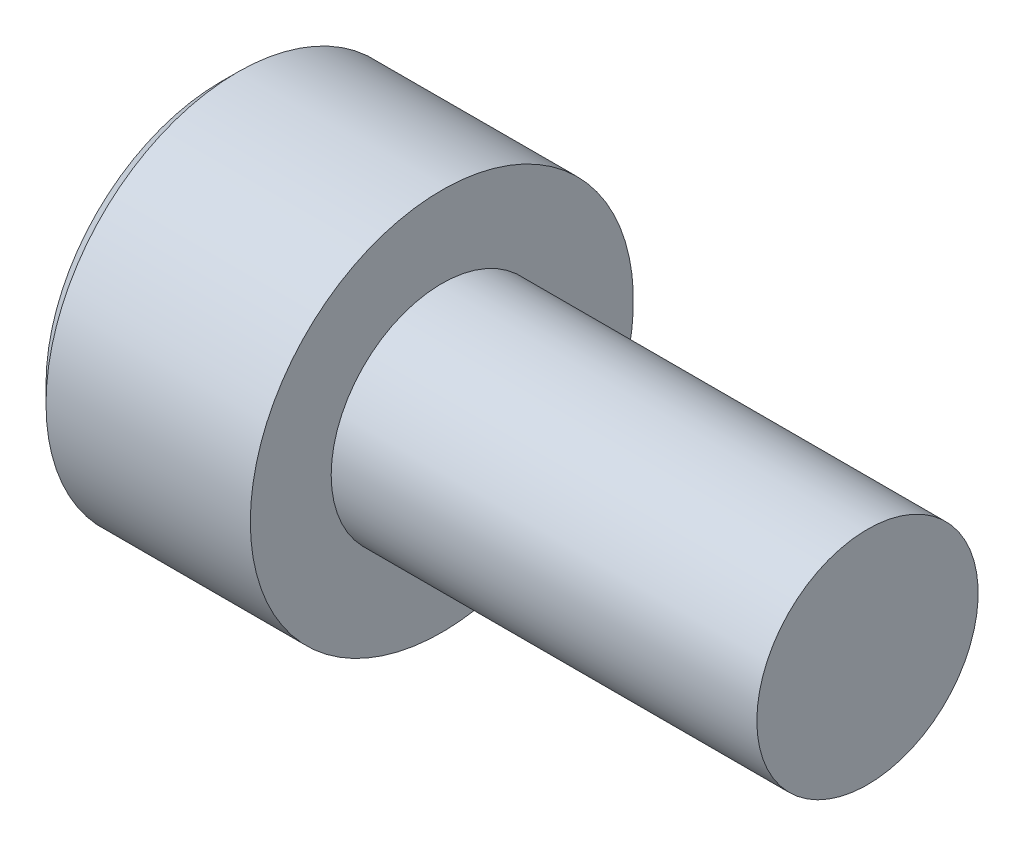
SolidWorks part; units mm, degrees
material "SCM435"
ref_plane "Front Plane" through (0, 0, 0) normal (0, 0, 1) x (1, 0, 0)
ref_plane "Top Plane" through (0, 0, 0) normal (0, 1, 0) x (1, 0, 0)
ref_plane "Right Plane" through (0, 0, 0) normal (1, 0, 0) x (0, 0, -1)
sketch "Sketch1" plane through (0, 0, 0) normal (0, 0, 1) x (1, 0, 0)
  line L2 (-2.6, 0) -> (5, 0)
  line L3 (5, 0) -> (5, 1.3)
  line L4 (5, 1.3) -> (0, 1.3)
  line L5 (0, 1.3) -> (0, 2.25)
  line L6 (0, 2.25) -> (-2.6, 2.25)
  line L7 (-2.6, 2.25) -> (-2.6, 0)
  line L8 (-2.6, 0) -> (5, 0) construction
  line L9 (0, 0) -> (0, 2.25) construction
  dimension "E" = 2.6
  dimension "L" = 5
  dimension "A" = 4.5
  dimension "M" = 2.6
revolve "Revolve1" add sketch "Sketch1" angle 360 about L8
cosmetic thread "Thread1" parameters "L_s"=5, "ATD"=2.1129
chamfer "Chamfer1" distance 0.2 angle 45 1 edges at (-2.6, 0, 2.25)
sketch "Sketch2" plane through (0, 0, 0) normal (0, 0, 1) x (1, 0, 0)
  line L0 (-0.8991, 0) -> (-1.5, 1)
  line L1 (-2.6, 0) -> (5, 0) construction
  line L2 (-1.5, 1) -> (-2.6, 1)
  line L3 (-2.6, 2.25) -> (-2.6, 0) construction
  line L4 (-2.6, 1) -> (-2.6, 0)
  line L5 (-2.6, 0) -> (-0.8991, 0) construction
  line L6 (-0.8991, 0) -> (-2.6, 0)
  dimension "FIX_3" = 59
  dimension "MSM_1" = 1.1
  dimension "B" = 2
revolve "Cut-Revolve1" cut sketch "Sketch2" angle 360 about L5
sketch "Sketch3" plane through (-2.6, 0, 0) normal (-1, 0, 0) x (0, 0, 1)
  line L0 (0, -1.1547) -> (0, 1.1547) construction
  line L1 (0, -1.1547) -> (1, -0.5774)
  line L2 (1, -0.5774) -> (1, 0.5774)
  line L3 (1, 0.5774) -> (0, 1.1547)
  line L4 (0, 1.1547) -> (-1, 0.5774)
  line L5 (-1, 0.5774) -> (-1, -0.5774)
  line L6 (-1, -0.5774) -> (0, -1.1547)
  line L7 (-1, 0) -> (1, 0) construction
  circle A0 centre (0, 0) radius 1 construction
  dimension "B" = 2
extrude "Cut-Extrude1" cut sketch "Sketch3" against normal blind 1.1
